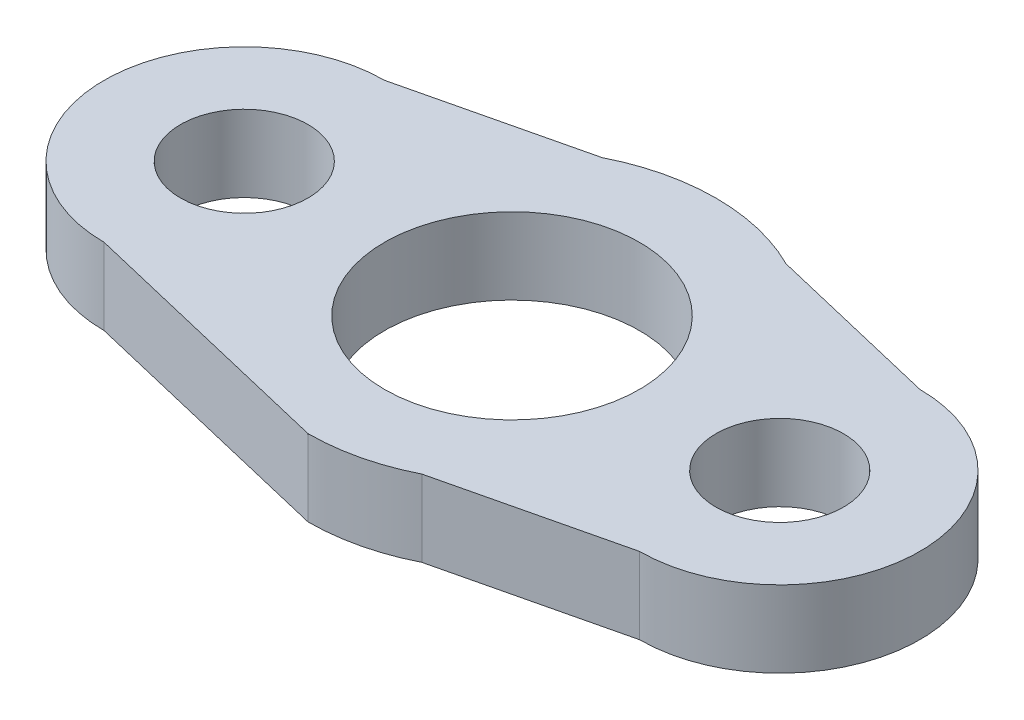
SolidWorks part; units mm, degrees
note: '?' marks a value the reader was unsure of.
ref_plane "Plan de face" through (0, 0, 0) normal (0, 0, 1) x (1, 0, 0)
ref_plane "Plan de dessus" through (0, 0, 0) normal (0, 1, 0) x (1, 0, 0)
ref_plane "Plan de droite" through (0, 0, 0) normal (1, 0, 0) x (0, 0, -1)
sketch "Esquisse1" plane through (0, 0, 0) normal (0, 1, 0) x (1, 0, 0)
  line L0 (0, 0) -> (30.1786, 0) construction
  line L1 (0, 0) -> (0, 13.8988) construction
  line L2 (-10.5, 5.5) -> (0, 8)
  line L3 (0, 8) -> (10.5, 5.5)
  line L4 (-10.5, -5.5) -> (0, -8)
  line L5 (0, -8) -> (10.5, -5.5)
  line L6 (-10.5, 0) -> (-10.5, 8.95) construction
  line L7 (10.5, 0) -> (10.5, 11.2901) construction
  circle A0 centre (0, 0) radius 5
  circle A1 centre (10.5, 0) radius 2.5
  circle A2 centre (-10.5, 0) radius 2.5
  circle A3 centre (-10.5, 0) radius 5.5
  circle A4 centre (0, 0) radius 8
  circle A5 centre (10.5, 0) radius 5.5
  dimension "D1" = 10
  dimension "D2" = 5
  dimension "D3" = 10.5
  dimension "D4" = 3
extrude "Boss.-Extru.2" add sketch "Esquisse1" along normal blind 3 contours A5 A4 L3 L2 A3 A0 | A3 A4 | A4 A3 A2 | A4 A3 L4 | A4 L2 A3 | A5 A0 A3 A4 L4 L5 | A4 A5 | L5 A4 | L3 A4 | L2 A4 | A5 A4 A1 | A5 L3 A4 | A5 A4 L5
ref_axis "Axe1" through (-10.5, 0, 0) along (0, 0, -1)?
